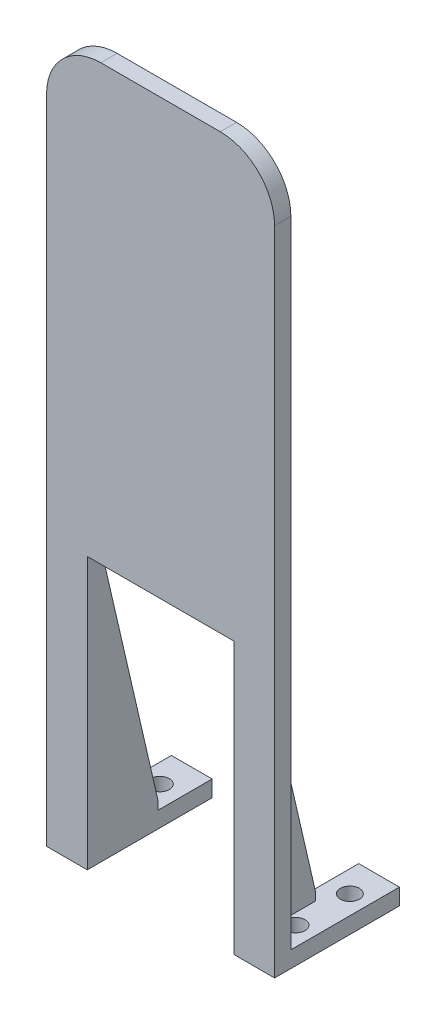
SolidWorks part; units mm, degrees
ref_plane "Front Plane" through (0, 0, 0) normal (0, 0, 1) x (1, 0, 0)
ref_plane "Top Plane" through (0, 0, 0) normal (0, 1, 0) x (1, 0, 0)
ref_plane "Right Plane" through (0, 0, 0) normal (1, 0, 0) x (0, 0, -1)
sketch "Sketch1" plane through (0, 0, 0) normal (0, 0, 1) x (1, 0, 0)
  line L1 (-21, 65) -> (21, 65)
  line L2 (-21, 65) -> (-21, -65)
  line L3 (-21, -65) -> (21, -65)
  line L4 (21, 65) -> (21, -65)
  line L5 (-21, 65) -> (21, -65) construction
  line L6 (-21, -65) -> (21, 65) construction
  point P0 (0, 0)
  dimension "D1" = 42
  dimension "D2" = 130
extrude "Boss-Extrude1" add sketch "Sketch1" along normal blind 3
sketch "Sketch2" plane through (0, 0, 3) normal (0, 0, 1) x (1, 0, 0)
  line L0 (-21, -65) -> (21, -65) construction
  line L1 (-13.5, -115) -> (13.5, -115)
  line L2 (-13.5, -115) -> (-13.5, -15)
  line L3 (-13.5, -15) -> (13.5, -15)
  line L4 (13.5, -115) -> (13.5, -15)
  line L5 (-13.5, -115) -> (13.5, -15) construction
  line L6 (-13.5, -15) -> (13.5, -115) construction
  point P0 (0, -65)
  dimension "D1" = 27
  dimension "D2" = 100
extrude "Cut-Extrude1" cut sketch "Sketch2" against normal blind 3
sketch "Sketch3" plane through (0, 0, 0) normal (0, 0, -1) x (-1, 0, 0)
  line L0 (-13.5, -65) -> (-13.5, -15) construction
  line L1 (-21, -65) -> (-13.5, -65)
  line L2 (-21, -65) -> (-21, -62)
  line L3 (-21, -62) -> (-15.5, -62)
  line L4 (-13.5, -65) -> (-13.5, -62)
  line L5 (21, 65) -> (21, -65) construction
  line L6 (13.5, -65) -> (21, -65)
  line L7 (13.5, -65) -> (13.5, -62)
  line L8 (15.5, -62) -> (21, -62)
  line L9 (21, -65) -> (21, -62)
  line L10 (-13.5, -62) -> (13.5, -62) construction
  line L11 (-13.5, -17) -> (13.5, -17) construction
  line L13 (-13.5, -62) -> (-13.5, -17)
  line L14 (-13.5, -17) -> (-15.5, -17)
  line L15 (-15.5, -62) -> (-15.5, -17)
  line L17 (13.5, -62) -> (13.5, -17)
  line L18 (13.5, -17) -> (15.5, -17)
  line L19 (15.5, -62) -> (15.5, -17)
  dimension "D1" = 3
  dimension "D2" = 2
  dimension "D3" = 2
  dimension "D4" = 45
extrude "Boss-Extrude2" add sketch "Sketch3" along normal blind 10
chamfer "Chamfer1" distance 10 angle 77 2 edges at (-14.5, -17, -10) (14.5, -17, -10) first distance on face at (-14.5, -17, -5) first distance on face at (14.5, -17, -5)
sketch "Sketch5" plane through (0, -65, 0) normal (0, -1, 0) x (1, 0, 0)
  line L0 (-17.5, -4.3686) -> (17.5, -4.3686) construction
  line L1 (0, -4.3686) -> (0, 0) construction
  circle A0 centre (-17.5, -4.3686) radius 1.75
  circle A1 centre (17.5, -4.3686) radius 1.75
  dimension "D2" = 3.5
  dimension "D3" = 3.5
  dimension "D1" = 35
extrude "Cut-Extrude2" cut sketch "Sketch5" against normal blind 10
sketch "Sketch6" plane through (0, 0, -10) normal (0, 0, -1) x (-1, 0, 0)
  line L0 (13.5, -60.3148) -> (13.5, -65) construction
  line L1 (21, -65) -> (13.5, -65)
  line L2 (21, -65) -> (21, -62)
  line L3 (21, -62) -> (13.5, -62)
  line L4 (13.5, -65) -> (13.5, -62)
  line L5 (-13.5, -65) -> (-13.5, -60.3148) construction
  line L6 (-13.5, -62) -> (-21, -62)
  line L7 (-13.5, -62) -> (-13.5, -65)
  line L8 (-13.5, -65) -> (-21, -65)
  line L9 (-21, -62) -> (-21, -65)
  line L10 (-13.5, -62) -> (13.5, -62) construction
  dimension "D1" = 3
extrude "Boss-Extrude3" add sketch "Sketch6" along normal blind 10
pattern_linear "LPattern1" count 2 spacing 10 along (0, 0, -1) of "Cut-Extrude2"
fillet "Fillet1" radius 10 2 edges at (-21, 65, 1.5) (21, 65, 1.5)
